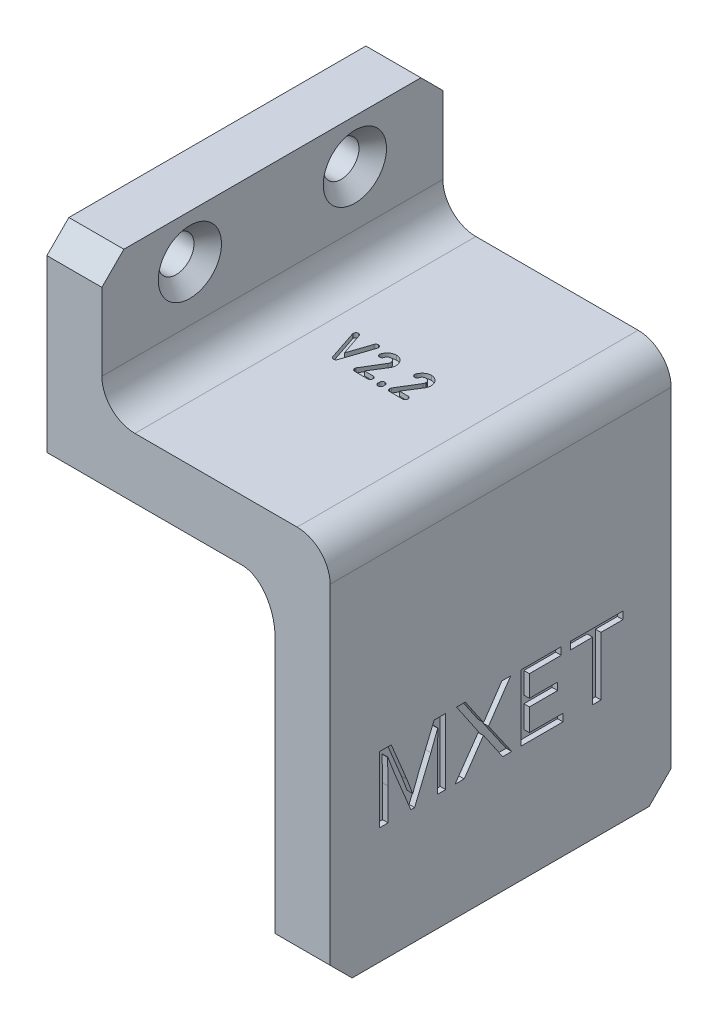
SolidWorks part; units mm, degrees
ref_plane "Front Plane" through (0, 0, 0) normal (0, 0, 1) x (1, 0, 0)
ref_plane "Top Plane" through (0, 0, 0) normal (0, 1, 0) x (1, 0, 0)
ref_plane "Right Plane" through (0, 0, 0) normal (1, 0, 0) x (0, 0, -1)
sketch "Sketch1" plane through (0, 0, 0) normal (0, 0, 1) x (1, 0, 0)
  line L0 (0, 30) -> (0, 47)
  line L1 (0, 47) -> (5, 47)
  line L2 (5, 47) -> (5, 35)
  line L3 (5, 35) -> (25.75, 35)
  line L4 (25.75, 35) -> (25.75, 0)
  line L5 (25.75, 0) -> (20.75, 0)
  line L6 (20.75, 0) -> (20.75, 30)
  line L7 (20.75, 30) -> (0, 30)
  dimension "D1" = 5
  dimension "D2" = 5
  dimension "D3" = 30
  dimension "D4" = 12
  dimension "D5" = 5
  dimension "D6" = 20.75
extrude "Boss-Extrude1" add sketch "Sketch1" along normal blind 31
sketch "Sketch2" plane through (20.75, 0, 0) normal (-1, 0, 0) x (0, 0, 1)
  line L0 (15.5, 30) -> (15.5, 0) construction
  line L1 (31, 30) -> (0, 30) construction
  line L2 (31, 0) -> (0, 0) construction
  line L5 (9.92, 2.925) -> (21.08, 21.075) construction
  circle A1 centre (21.08, 21.075) radius 0.625
  circle A2 centre (9.92, 2.925) radius 0.625
  point P0 (21.08, 21.075)
  point P3 (9.92, 2.925)
  point P4 (15.5, 15)
  dimension "D1" = 1.25
  dimension "D2" = 12.075
  dimension "D3" = 6.075
  dimension "D4" = 5.58
  dimension "D5" = 5.58
extrude "Holes - leftHand assembly" cut sketch "Sketch2" against normal blind 4
fillet "Fillet1" radius 3 2 edges at (5, 35, 15.5) (25.75, 35, 15.5)
sketch "Sketch3" plane through (5, 0, 0) normal (1, 0, 0) x (0, 0, -1)
  line L0 (-23, 43) -> (-8, 43) construction
  line L1 (-31, 47) -> (0, 47) construction
  circle A0 centre (-23, 43) radius 1.625
  circle A1 centre (-8, 43) radius 1.625
  point P4 (-15.5, 43)
  point P7 (-15.5, 47)
  dimension "D2" = 3.25
  dimension "D1" = 15
  dimension "D3" = 4
extrude "Cut-Extrude2" cut sketch "Sketch3" against normal through all
sketch "Sketch4" plane through (0, 0, 0) normal (-1, 0, 0) x (0, 0, 1)
  line L0 (0, 30) -> (0, 27.5)
  line L1 (0, 30) -> (0, 0) construction
  line L2 (0, 30) -> (31, 30)
  line L3 (31, 30) -> (31, 27.5)
  line L4 (31, 30) -> (31, 0) construction
  line L5 (31, 30) -> (31, 0) construction
  arc A0 (0, 27.5) -> (31, 27.5) centre (15.5, -40.7624) cw
  dimension "D1" = 70
  dimension "D2" = 2.5
extrude "Boss-Extrude2" add sketch "Sketch4" against normal up to surface (20.75 mm away) up to face at (20.75, 2.925, 10.545)
chamfer "Chamfer1" distance 2 angle 45 2 edges at (10.375, 27.5, 0) (10.375, 27.5, 31) first distance on face at (10.375, 28.3688, 15.5) first distance on face at (13.375, 28.9, 31)
fillet "Fillet2" radius 3 3 edges at (20.75, 28.6766, 30.1766) (20.75, 28.546, 0.9928) (20.75, 29.2374, 15.6727)
chamfer "Chamfer2" distance 2 angle 45 4 edges at (23.25, 0, 31) (23.25, 0, 0) (2.5, 47, 0) (2.5, 47, 31)
sketch "Sketch5" plane through (25.75, 0, 0) normal (1, 0, 0) x (0, 0, -1)
  text T0 "MXET" font "Corbel" height 6
extrude "Cut-Extrude3" cut sketch "Sketch5" against normal blind 0.5
fillet "Fillet3" radius 5 4 edges at (19.4572, 27.2735, 29.5274) (19.5244, 27.3058, 1.8717) (8.875, 27.8532, 29.3532) (8.875, 27.9207, 1.9856)
chamfer "Chamfer3" distance 1.25 angle 45 2 edges at (5, 44.625, 23) (5, 44.625, 8)
sketch "Sketch7" plane through (20.75, 0, 0) normal (-1, 0, 0) x (0, 0, 1)
  circle A0 centre (11.91, 21.085) radius 0.625
  circle A1 centre (23.07, 2.935) radius 0.625
  point P0 (11.91, 21.085)
  point P1 (23.07, 2.935)
  dimension "D1" = 1.25
extrude "Holes - Right Hand assy" cut sketch "Sketch7" against normal blind 4
sketch "Sketch8" plane through (20.75, 0, 0) normal (-1, 0, 0) x (0, 0, 1)
  line L0 (15.8247, 16.8401) -> (13.7063, 19.6302)
  line L2 (12.9696, 19.0709) -> (15.088, 16.2808)
  line L3 (15.088, 16.2808) -> (15.8247, 16.8401)
  line L4 (18.8463, 8.4536) -> (21.5477, 4.8956)
  line L6 (22.2409, 5.422) -> (19.5395, 8.9799)
  line L7 (19.5395, 8.9799) -> (18.8463, 8.4536)
  line L8 (11.9695, 18.3115) -> (12.3601, 20.3042)
  line L9 (12.3601, 20.3042) -> (14.594, 20.3042)
  line L10 (14.594, 20.3042) -> (13.7063, 19.6302)
  line L11 (11.9695, 18.3115) -> (12.9696, 19.0709)
  line L12 (22.2409, 5.422) -> (23.2249, 6.1691)
  line L13 (23.2249, 6.1691) -> (22.6912, 4.1523)
  line L14 (22.6912, 4.1523) -> (20.5687, 4.1523)
  line L15 (20.5687, 4.1523) -> (21.5477, 4.8956)
  text T0 "RH" font "DYMO Symbols" height 5
extrude "Cut-Extrude5" cut sketch "Sketch8" against normal blind 0.5
sketch "Sketch9" plane through (20.75, 0, 0) normal (-1, 0, 0) x (0, 0, 1)
  line L0 (36.02, 22.95) -> (7.92, 22.95) construction
  line L1 (9.5, 23.25) -> (21.5, 23.25)
  line L2 (9.5, 23.25) -> (9.5, 24.5)
  line L3 (9.5, 24.5) -> (21.5, 24.5)
  line L4 (21.5, 23.25) -> (21.5, 24.5)
  line L5 (29, 0) -> (2, 0) construction
  line L6 (9.5, 0) -> (21.5, 0)
  line L7 (9.5, 0) -> (9.5, 0.75)
  line L8 (9.5, 0.75) -> (21.5, 0.75)
  line L9 (21.5, 0) -> (21.5, 0.75)
  line L10 (7.92, 1.05) -> (36.02, 1.05) construction
  line L11 (9.5, 24.5) -> (0, 24.5) construction
  line L12 (0, 25.6258) -> (0, 2) construction
  line L13 (21.5, 24.5) -> (31, 24.5) construction
  line L14 (31, 25.2574) -> (31, 2) construction
  dimension "D1" = 0.3
  dimension "D2" = 0.3
  dimension "D3" = 12
  dimension "D4" = 1.25
extrude "Boss-Extrude3" add sketch "Sketch9" along normal blind 1
sketch "Sketch11" plane through (0, 35, 0) normal (0, 1, 0) x (1, 0, 0)
  text T0 "V2.2" font "DS ISO 1" height 3.175
extrude "version" cut sketch "Sketch11" against normal blind 0.4
